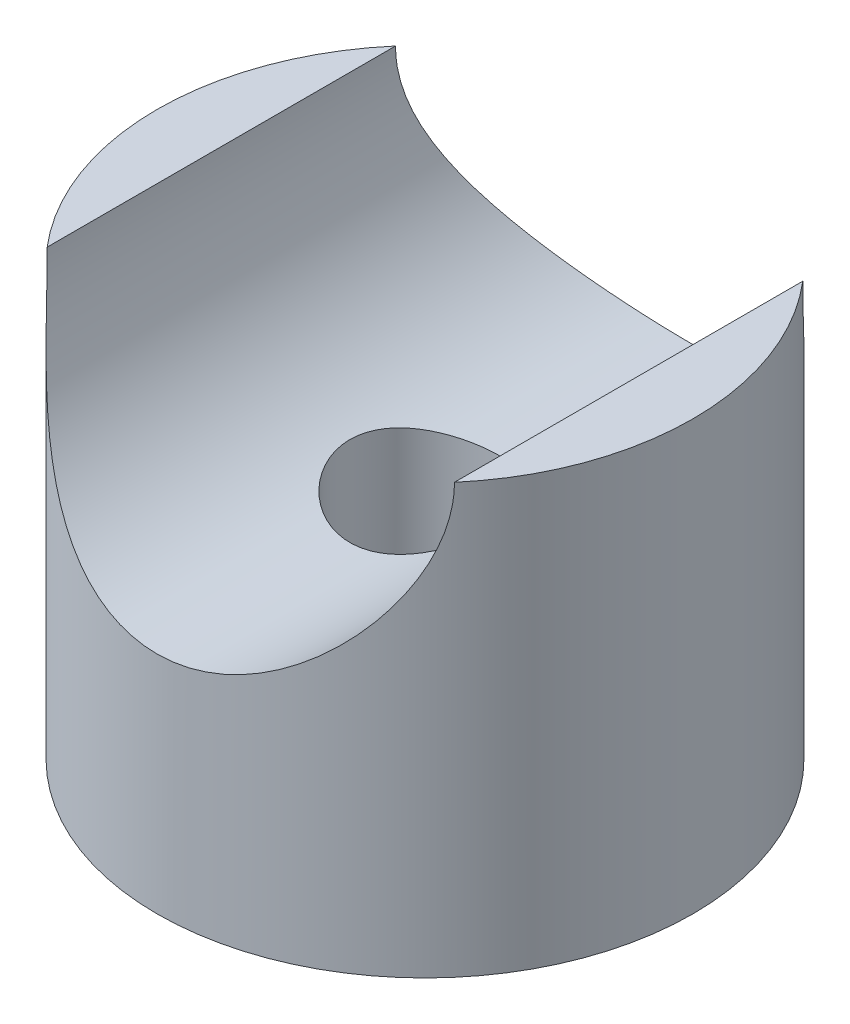
SolidWorks part; units mm, degrees
ref_plane "Front Plane" through (0, 0, 0) normal (0, 0, 1) x (1, 0, 0)
ref_plane "Top Plane" through (0, 0, 0) normal (0, 1, 0) x (1, 0, 0)
ref_plane "Right Plane" through (0, 0, 0) normal (1, 0, 0) x (0, 0, -1)
sketch "Sketch1" plane through (0, 0, 0) normal (0, 1, 0) x (1, 0, 0)
  circle A0 centre (0, 0) radius 12.5
  circle A1 centre (0, 0) radius 3.5
  dimension "D1" = 25
extrude "Boss-Extrude1" add sketch "Sketch1" along normal blind 20
sketch "Sketch2" plane through (0, 0, 0) normal (0, 0, 1) x (1, 0, 0)
  line L0 (12.5, 20) -> (-12.5, 20) construction
  circle A0 centre (0, 20) radius 9.5
  dimension "D1" = 19
extrude "Cut-Extrude1" cut sketch "Sketch2" against normal blind 22 and the other way blind 22
